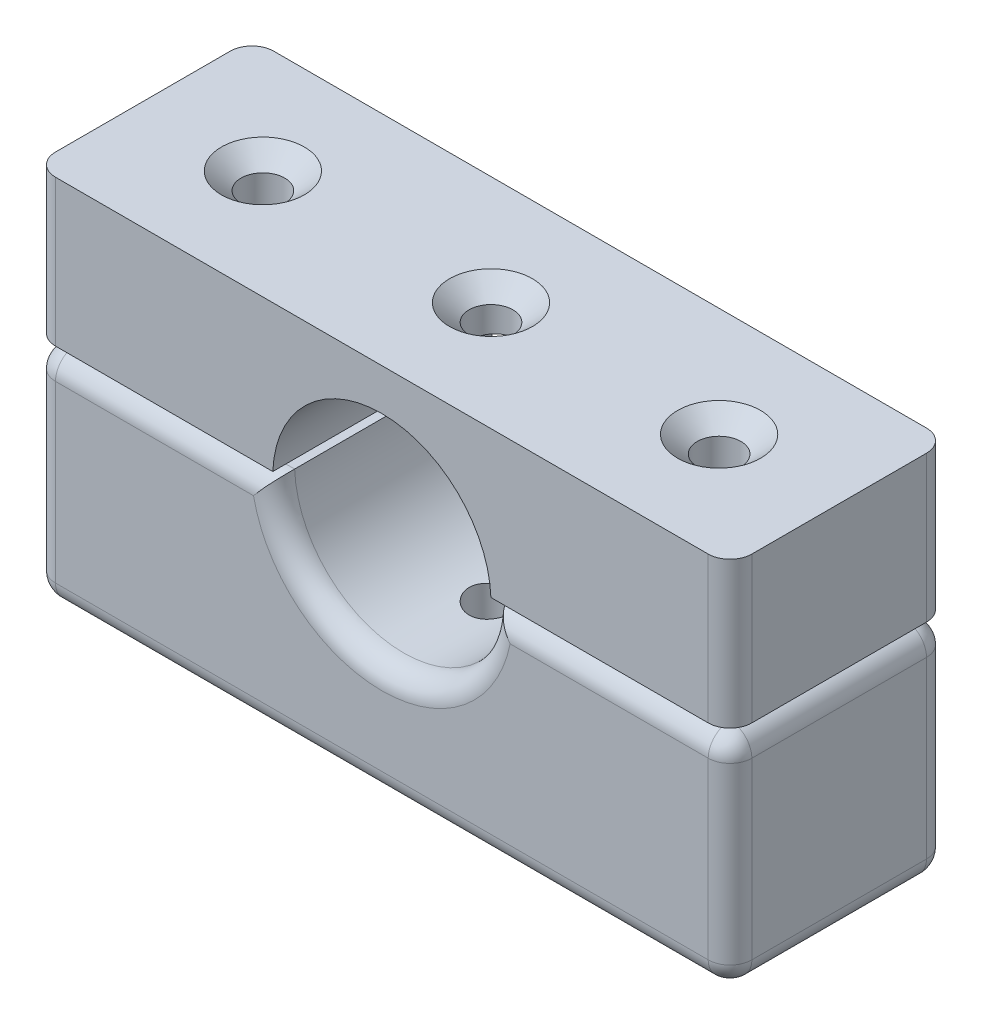
SolidWorks part; units mm, degrees
ref_plane "Front Plane" through (0, 0, 0) normal (0, 0, 1) x (1, 0, 0)
ref_plane "Top Plane" through (0, 0, 0) normal (0, 1, 0) x (1, 0, 0)
ref_plane "Right Plane" through (0, 0, 0) normal (1, 0, 0) x (0, 0, -1)
sketch "Sketch2" plane through (0, 0, 0) normal (0, 0, 1) x (1, 0, 0)
  line L0 (0, 26.416) -> (81.026, 26.416)
  line L1 (0, 0) -> (81.026, 0)
  line L2 (0, 0) -> (0, 25.4)
  line L3 (0, 25.4) -> (81.026, 25.4)
  line L4 (81.026, 0) -> (81.026, 25.4)
  line L5 (40.513, 43.434) -> (40.513, 0) construction
  line L6 (0, 26.416) -> (81.026, 26.416)
  line L7 (0, 26.416) -> (0, 43.434)
  line L8 (0, 43.434) -> (81.026, 43.434)
  line L9 (81.026, 26.416) -> (81.026, 43.434)
  line L10 (0, 26.416) -> (0, 25.4) construction
  line L11 (0, 25.908) -> (81.026, 25.908) construction
  circle A0 centre (40.513, 25.908) radius 12.7
  dimension "D5" = 25.4
  dimension "D1" = 25.4
  dimension "D2" = 81.026
  dimension "D3" = 1.016
  dimension "D4" = 17.018
extrude "Boss-Extrude1" add sketch "Sketch2" along normal blind 25.4 contours A0 L0 L9 L8 L7 | A0 L3 L2 L1 L4 region at (0.8279, 34.925, 0) region at (40.513, 11.7022, 0)
sketch "Sketch3" plane through (0, 43.434, 0) normal (0, 1, 0) x (1, 0, 0)
  line L0 (0, -12.7) -> (81.026, -12.7) construction
  line L1 (0, -25.4) -> (0, 0) construction
  line L2 (81.026, -25.4) -> (81.026, 0) construction
  line L3 (40.513, 0) -> (40.513, -25.4) construction
  line L4 (0, 0) -> (81.026, 0) construction
  line L5 (0, -25.4) -> (81.026, -25.4) construction
  circle A0 centre (40.513, -12.7) radius 4.826
  circle A1 centre (40.513, -12.7) radius 2.54
  circle A2 centre (13.97, -12.7) radius 2.54
  circle A3 centre (13.97, -12.7) radius 4.826
  circle A4 centre (67.056, -12.7) radius 2.54
  circle A5 centre (67.056, -12.7) radius 4.826
  dimension "D2" = 5.08
  dimension "D3" = 9.652
  dimension "D4" = 5.08
  dimension "D5" = 9.652
  dimension "D1" = 13.97
extrude "Cut-Extrude1" cut sketch "Sketch3" against normal up to surface (43.434 mm away) contours A2 | A1 | A4 region at (40.513, 43.434, 12.7) region at (13.97, 43.434, 12.7) region at (67.056, 43.434, 12.7) up to face at (40.513, 0, 12.7)
extrude "Cut-Extrude2" cut sketch "Sketch3<3>" against normal blind 3.2258 draft 49 contours A3 A2 | A2 | A0 A1 | A1 | A5 A4 | A4 region at (35.8235, 43.434, 12.7) region at (40.513, 43.434, 12.7) region at (13.97, 43.434, 12.7) region at (9.2805, 43.434, 12.7) region at (67.056, 43.434, 12.7) region at (62.3665, 43.434, 12.7)
sketch "Sketch3<3>" plane through (0, 43.434, 0) normal (0, 1, 0) x (1, 0, 0) same geometry as "Sketch3"
fillet "Fillet1" radius 2.54 12 edges at (81.026, 25.4, 12.7) (81.026, 12.7, 0) (67.1144, 25.4, 0) (40.513, 13.208, 0) (13.9116, 25.4, 0) (0, 12.7, 0) (0, 25.4, 12.7) (0, 12.7, 25.4) (81.026, 12.7, 25.4) (67.1144, 25.4, 25.4) (40.513, 13.208, 25.4) (13.9116, 25.4, 25.4)
fillet "Fillet2" radius 2.54 4 edges at (81.026, 34.925, 25.4) (81.026, 34.925, 0) (0, 34.925, 0) (0, 34.925, 25.4)
fillet "Fillet3" radius 2.54 8 edges at (0.7439, 0, 24.6561) (0, 0, 12.7) (0.7439, 0, 0.7439) (40.513, 0, 0) (80.2821, 0, 0.7439) (81.026, 0, 12.7) (80.2821, 0, 24.6561) (40.513, 0, 25.4)
